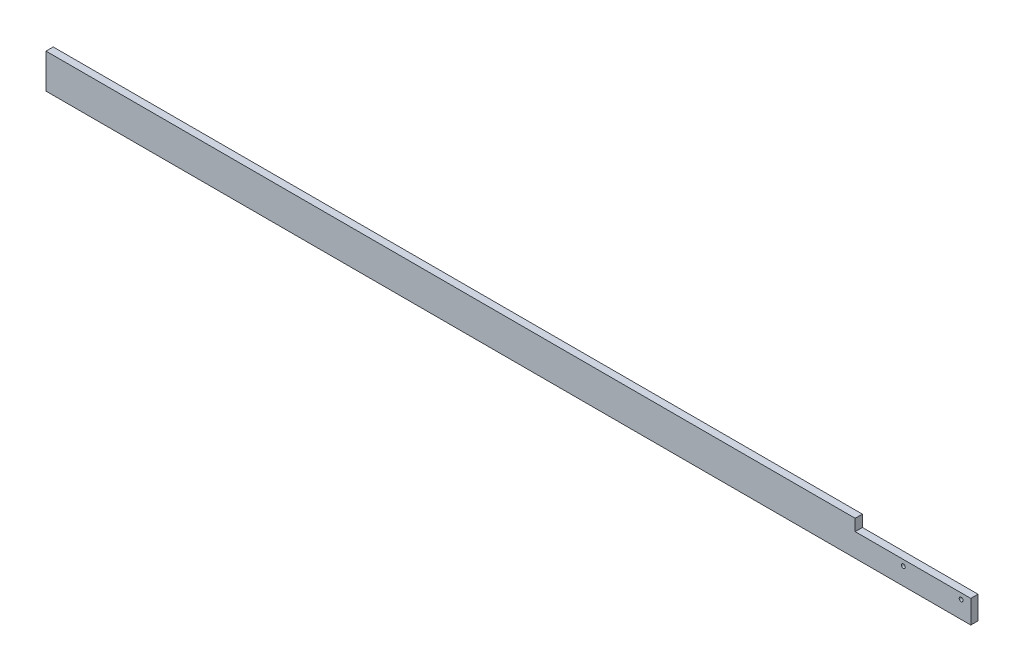
SolidWorks part; units mm, degrees
ref_plane "Front Plane" through (0, 0, 0) normal (0, 0, 1) x (1, 0, 0)
ref_plane "Top Plane" through (0, 0, 0) normal (0, 1, 0) x (1, 0, 0)
ref_plane "Right Plane" through (0, 0, 0) normal (1, 0, 0) x (0, 0, -1)
sketch "Sketch1" plane through (0, 0, 0) normal (0, 0, 1) x (1, 0, 0)
  line L1 (-304.8, -11.43) -> (304.8, -11.43)
  line L2 (-304.8, -11.43) -> (-304.8, 11.43)
  line L3 (-304.8, 11.43) -> (304.8, 11.43)
  line L4 (304.8, -11.43) -> (304.8, 11.43)
  line L5 (-304.8, -11.43) -> (304.8, 11.43) construction
  line L6 (-304.8, 11.43) -> (304.8, -11.43) construction
  point P0 (0, 0)
  dimension "D1" = 609.6
  dimension "D2" = 22.86
extrude "Boss-Extrude1" add sketch "Sketch1" along normal mid plane 4.7625
sketch "Sketch2" [suppressed] plane through (0, 0, 2.3813) normal (0, 0, 1) x (1, 0, 0)
  line L0 (304.8, -11.43) -> (304.8, 11.43) construction
  line L1 (304.8, 11.43) -> (228.6, 11.43)
  line L2 (304.8, 11.43) -> (304.8, -3.81)
  line L3 (304.8, -3.81) -> (228.6, -3.81)
  line L4 (228.6, 11.43) -> (228.6, -3.81)
  circle A0 centre (260.35, -7.62) radius 1.27
  circle A1 centre (298.45, -7.62) radius 1.27
  dimension "D6" = 2.54
  dimension "D7" = 2.54
  dimension "D1" = 15.24
  dimension "D2" = 76.2
  dimension "D3" = 44.45
  dimension "D4" = 6.35
  dimension "D5" = 3.81
extrude "Cut-Extrude1" [suppressed] cut sketch "Sketch2" against normal through all
sketch "Sketch3" plane through (0, 0, 2.3813) normal (0, 0, 1) x (1, 0, 0)
  line L0 (304.8, -11.43) -> (304.8, 11.43) construction
  line L1 (304.8, 11.43) -> (228.6, 11.43)
  line L2 (304.8, 11.43) -> (304.8, 3.81)
  line L3 (304.8, 3.81) -> (228.6, 3.81)
  line L4 (228.6, 11.43) -> (228.6, 3.81)
  circle A0 centre (260.35, 0) radius 1.27
  circle A1 centre (298.45, 0) radius 1.27
  dimension "D3" = 2.54
  dimension "D4" = 2.54
  dimension "D1" = 7.62
  dimension "D2" = 76.2
  dimension "D5" = 3.81
  dimension "D6" = 38.1
  dimension "D7" = 6.35
extrude "Cut-Extrude2" cut sketch "Sketch3" against normal through all
sketch "Sketch4" [suppressed] plane through (0, 0, 2.3813) normal (0, 0, 1) x (1, 0, 0)
  line L0 (304.8, 11.43) -> (-304.8, 11.43) construction
  line L1 (304.8, -11.43) -> (304.8, 11.43) construction
  circle A0 centre (260.35, 7.62) radius 1.27
  circle A1 centre (298.45, 7.62) radius 1.27
  dimension "D1" = 2.54
  dimension "D2" = 2.54
  dimension "D3" = 3.81
  dimension "D4" = 6.35
  dimension "D5" = 44.45
extrude "Cut-Extrude3" [suppressed] cut sketch "Sketch4" against normal through all
